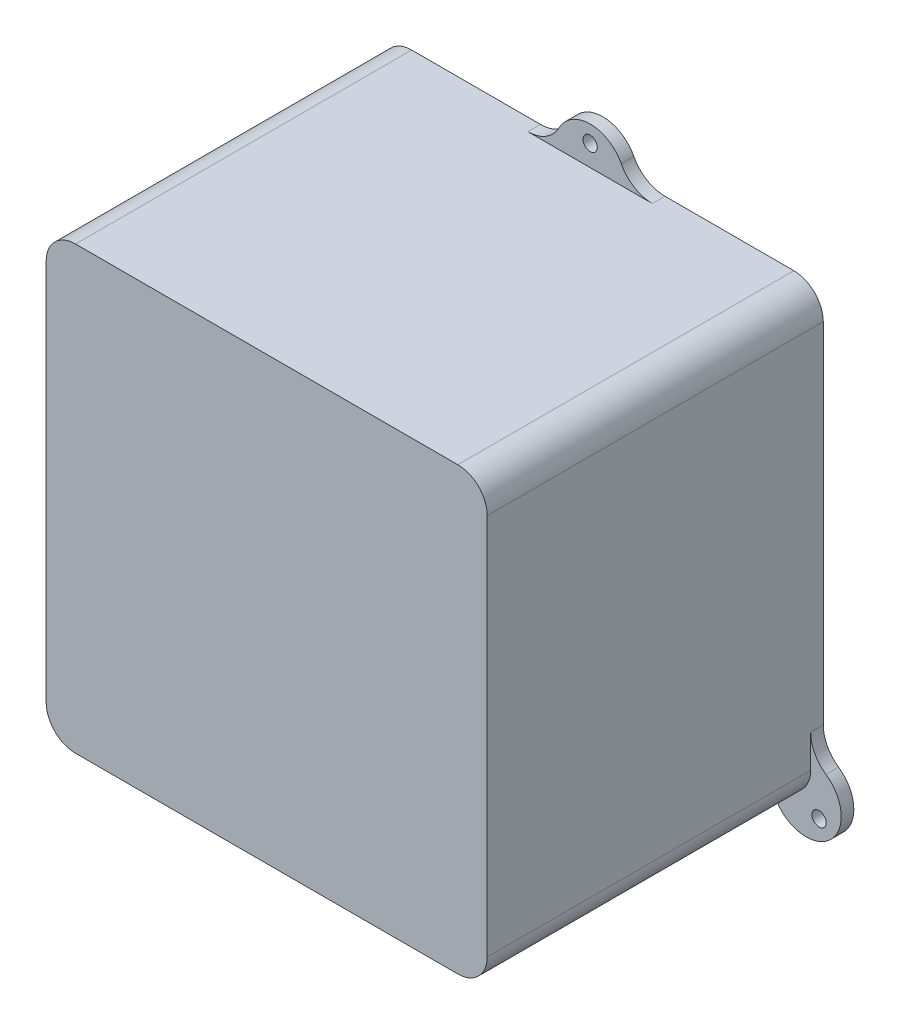
SolidWorks part; units mm, degrees
ref_plane "Plan de face" through (0, 0, 0) normal (0, 0, 1) x (1, 0, 0)
ref_plane "Plan de dessus" through (0, 0, 0) normal (0, 1, 0) x (1, 0, 0)
ref_plane "Plan de droite" through (0, 0, 0) normal (1, 0, 0) x (0, 0, -1)
sketch "Esquisse1" plane through (0, 0, 0) normal (0, 0, 1) x (1, 0, 0)
  line L1 (0, 0) -> (105, 0)
  line L2 (0, 0) -> (0, 105)
  line L3 (0, 105) -> (105, 105)
  line L4 (105, 0) -> (105, 105)
  dimension "D1" = 105
  dimension "D2" = 105
extrude "Boss.-Extru.1" add sketch "Esquisse1" along normal blind 80
sketch "Esquisse2" plane through (0, 0, 0) normal (0, 0, -1) x (-1, 0, 0)
  line L8 (-7, 7) -> (-7, 98)
  line L9 (-7, 98) -> (-98, 98)
  line L10 (-98, 98) -> (-98, 7)
  line L11 (-98, 7) -> (-7, 7)
  line L12 (-7, 7) -> (-7, 98)
  line L13 (-7, 98) -> (-98, 98)
  line L14 (-98, 98) -> (-98, 7)
  line L15 (-98, 7) -> (-7, 7)
  dimension "D1" = 7
extrude "Enlèv. mat.-Extru.1" cut sketch "Esquisse2" against normal offset from surface (70 mm away) 10 up to face at (52.5, 52.5, 80)
sketch "Esquisse3" plane through (0, 0, 80) normal (0, 0, 1) x (1, 0, 0)
  line L0 (100, 100) -> (5, 100)
  line L1 (5, 100) -> (5, 5)
  line L2 (5, 5) -> (100, 5)
  line L3 (100, 5) -> (100, 100)
  line L4 (0, 105) -> (0, 0)
  line L5 (0, 0) -> (105, 0)
  line L6 (105, 0) -> (105, 105)
  line L7 (105, 105) -> (0, 105)
  line L8 (0, 105) -> (0, 0)
  line L9 (0, 0) -> (105, 0)
  line L10 (105, 0) -> (105, 105)
  line L11 (105, 105) -> (0, 105)
  dimension "D1" = 0
  dimension "D2" = 5
extrude "Boss.-Extru.2" [suppressed] add sketch "Esquisse3" along normal blind 10
sketch "Esquisse4" plane through (0, 0, 0) normal (0, 0, -1) x (-1, 0, 0)
  line L0 (-98, 7) -> (-118.7207, -13.7207) construction
  line L1 (-7, 7) -> (8.1122, -8.1122) construction
  line L6 (0, 0) -> (-105, 0) construction
  line L7 (0.7972, -8.8596) -> (10.9788, 1.3219) construction
  line L8 (-114.7245, 0.0676) -> (-101.0769, -13.5799) construction
  line L9 (-52.5, 98) -> (-52.5, 115.4924) construction
  line L10 (-7, 98) -> (-98, 98) construction
  line L11 (-105, 105) -> (0, 105) construction
  line L12 (-62.0341, 114) -> (-40.7837, 114) construction
  line L13 (-49.1534, 98) -> (-55.8466, 98)
  circle A0 centre (-107, -2) radius 1.5
  circle A1 centre (2, -2) radius 1.5
  circle A2 centre (-1.0759, 1.0759) radius 8.35
  circle A3 centre (-103.9241, 1.0759) radius 8.35
  circle A4 centre (-52.5, 110) radius 1.5
  arc A5 (-49.1534, 98) -> (-55.8466, 98) centre (-52.5, 105.65) ccw
  point P28 (-52.5, 105)
  dimension "D1" = 3
  dimension "D4" = 3
  dimension "D7" = 16.7
  dimension "D8" = 16.7
  dimension "D10" = 3
  dimension "D12" = 16.7
  dimension "D2" = 2
  dimension "D3" = 4
  dimension "D5" = 2
  dimension "D6" = 4
  dimension "D9" = 5
  dimension "D11" = 4
extrude "Boss.-Extru.3" add sketch "Esquisse4" against normal blind 3
fillet "Congé1" radius 7 4 edges at (105, 0, 41.5) (0, 105, 40) (0, 0, 41.5) (105, 105, 40)
fillet "Congé3" [suppressed] radius 1 type face fillet
fillet "Congé4" radius 8.35 6 edges at (9.3563, 0, 1.5) (0, 9.3563, 1.5) (95.6437, 0, 1.5) (105, 9.3563, 1.5) (60.8247, 105, 1.5) (44.1753, 105, 1.5)
hole_wizard "Dégagement M31" positions "Esquisse5" profile "Esquisse6" hole size "M3" standard "ISO" end condition up to next
sketch "Esquisse5" plane through (0, 0, 3) normal (0, 0, 1) x (1, 0, 0)
  point P0 (107, -2)
  point P3 (-2, -2)
  point P6 (52.5, 110)
sketch "Esquisse6" plane through (107, -2, 3) normal (1, 0, 0) x (0, -1, 0)
  line L0 (0, 0) -> (0, 3)
  line L1 (0, 3) -> (1.7, 3)
  line L2 (1.7, 3) -> (1.7, 0)
  line L5 (1.7, 0) -> (0, 0)
  line L11 (0, -6.35) -> (0, 107.95) construction
  dimension "Diamètre du perçage jusqu'au prochain" = 3.4
  dimension "Profondeur du perçage jusqu'au prochain" = 3
